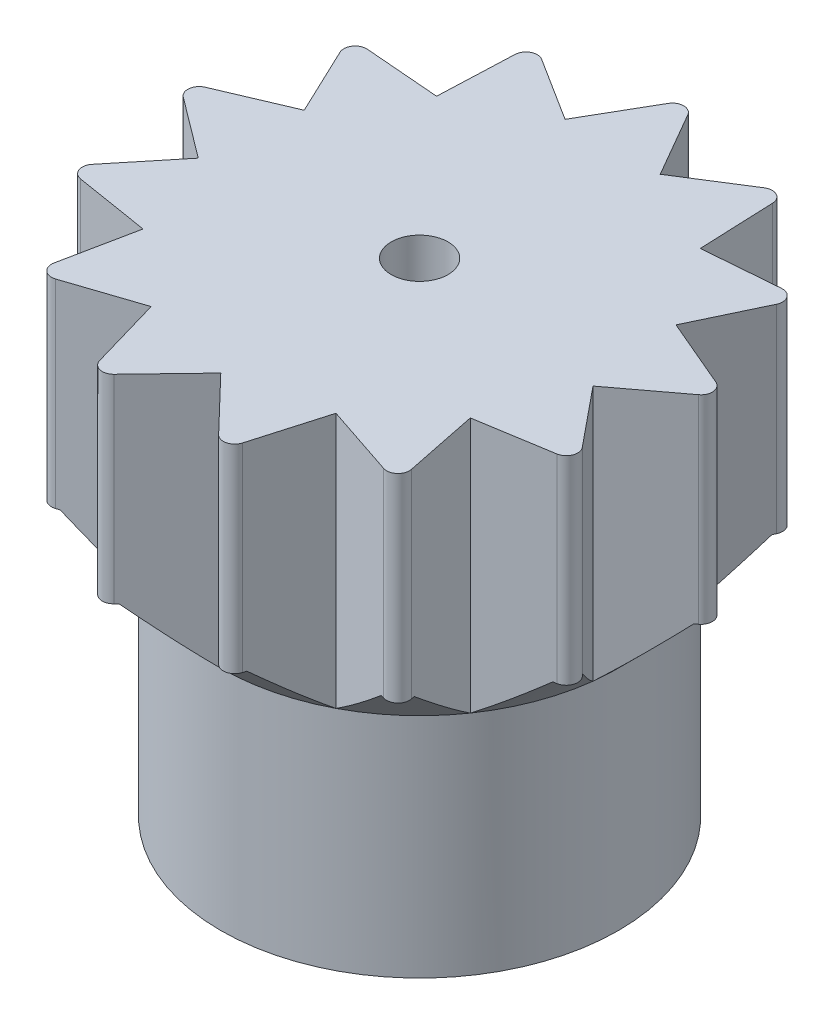
SolidWorks part; units mm, degrees
ref_plane "Front" through (0, 0, 0) normal (0, 0, 1) x (1, 0, 0)
ref_plane "Top" through (0, 0, 0) normal (0, 1, 0) x (1, 0, 0)
ref_plane "Right" through (0, 0, 0) normal (1, 0, 0) x (0, 0, -1)
sketch "Sketch1" plane through (0, 0, 0) normal (0, 1, 0) x (1, 0, 0)
  line L0 (2.3209, 2.6198) -> (3.9907, 2.7546)
  line L1 (3.9907, 2.7546) -> (3.2726, 1.2411)
  line L2 (3.2726, 1.2411) -> (4.8137, 0.5845)
  line L3 (4.8137, 0.5845) -> (3.4745, -0.4219)
  line L4 (3.4745, -0.4219) -> (4.534, -1.7195)
  line L5 (4.534, -1.7195) -> (2.8804, -1.9882)
  line L6 (2.8804, -1.9882) -> (3.2155, -3.6296)
  line L7 (3.2155, -3.6296) -> (1.6265, -3.0991)
  line L8 (1.6265, -3.0991) -> (1.1605, -4.7082)
  line L9 (1.1605, -4.7082) -> (0, -3.5)
  line L10 (0, -3.5) -> (-1.1605, -4.7082)
  line L11 (-1.1605, -4.7082) -> (-1.6265, -3.0991)
  line L12 (-1.6265, -3.0991) -> (-3.2155, -3.6296)
  line L13 (-3.2155, -3.6296) -> (-2.8804, -1.9882)
  line L14 (-2.8804, -1.9882) -> (-4.534, -1.7195)
  line L15 (-4.534, -1.7195) -> (-3.4745, -0.4219)
  line L16 (-3.4745, -0.4219) -> (-4.8137, 0.5845)
  line L17 (-4.8137, 0.5845) -> (-3.2726, 1.2411)
  line L18 (-3.2726, 1.2411) -> (-3.9907, 2.7546)
  line L19 (-3.9907, 2.7546) -> (-2.3209, 2.6198)
  line L20 (-2.3209, 2.6198) -> (-2.2535, 4.2936)
  line L21 (-2.2535, 4.2936) -> (-0.8376, 3.3983)
  line L22 (-0.8376, 3.3983) -> (0, 4.8491)
  line L23 (0, 4.8491) -> (0.8376, 3.3983)
  line L24 (0.8376, 3.3983) -> (2.2535, 4.2936)
  line L25 (2.2535, 4.2936) -> (2.3209, 2.6198)
  line L26 (-0.8376, 3.3983) -> (0.8376, 3.3983) construction
  circle A0 centre (0, 0) radius 3.5 construction
  circle A1 centre (0, 0) radius 0.5
  point P44 (0, 0)
  dimension "D2" = 7
  dimension "D4" = 1
  dimension "D3" = 60
  dimension "D5" = 1.6752
  dimension "D6" = 1.4508
  dimension "D1" = 13
extrude "Boss-Extrude1" add sketch "Sketch1" along normal blind 3.5
sketch "Sketch3" plane through (0, 0, 0) normal (0, -1, 0) x (1, 0, 0)
  circle A0 centre (0, 0) radius 3.5
  circle A1 centre (0, 0) radius 0.5
extrude "Boss-Extrude2" add sketch "Sketch3" along normal blind 5
sketch "Sketch2" plane through (0, -5, 0) normal (0, -1, 0) x (1, 0, 0)
  line L168 (-2.3565, -0.3552) -> (-2.394, -0.7385)
  line L169 (-2.5053, 0) -> (-2.3565, -0.3552)
  line L170 (-2.3565, 0.3552) -> (-2.5053, 0)
  line L171 (-2.394, 0.7385) -> (-2.3565, 0.3552)
  line L172 (-2.1471, 1.034) -> (-2.394, 0.7385)
  line L173 (-2.07, 1.4113) -> (-2.1471, 1.034)
  line L174 (-1.747, 1.6209) -> (-2.07, 1.4113)
  line L175 (-1.562, 1.9587) -> (-1.747, 1.6209)
  line L176 (-1.1916, 2.0639) -> (-1.562, 1.9587)
  line L177 (-0.9153, 2.3321) -> (-1.1916, 2.0639)
  line L178 (-0.5303, 2.3234) -> (-0.9153, 2.3321)
  line L179 (-0.1872, 2.4983) -> (-0.5303, 2.3234)
  line L180 (0.1781, 2.3765) -> (-0.1872, 2.4983)
  line L181 (0.5575, 2.4425) -> (0.1781, 2.3765)
  line L182 (0.8707, 2.2184) -> (0.5575, 2.4425)
  line L183 (1.2527, 2.1697) -> (0.8707, 2.2184)
  line L184 (1.4859, 1.8632) -> (1.2527, 2.1697)
  line L185 (1.8365, 1.704) -> (1.4859, 1.8632)
  line L186 (1.969, 1.3425) -> (1.8365, 1.704)
  line L187 (2.2572, 1.087) -> (1.969, 1.3425)
  line L188 (2.2773, 0.7024) -> (2.2572, 1.087)
  line L189 (2.4773, 0.3734) -> (2.2773, 0.7024)
  line L190 (2.3831, 0) -> (2.4773, 0.3734)
  line L191 (2.4773, -0.3734) -> (2.3831, 0)
  line L192 (2.2773, -0.7024) -> (2.4773, -0.3734)
  line L193 (2.2572, -1.087) -> (2.2773, -0.7024)
  line L194 (1.969, -1.3425) -> (2.2572, -1.087)
  line L195 (1.8365, -1.704) -> (1.969, -1.3425)
  line L196 (1.4859, -1.8632) -> (1.8365, -1.704)
  line L197 (1.2527, -2.1697) -> (1.4859, -1.8632)
  line L198 (0.8707, -2.2184) -> (1.2527, -2.1697)
  line L199 (0.5575, -2.4425) -> (0.8707, -2.2184)
  line L200 (0.1781, -2.3765) -> (0.5575, -2.4425)
  line L201 (-0.1872, -2.4983) -> (0.1781, -2.3765)
  line L202 (-0.5303, -2.3234) -> (-0.1872, -2.4983)
  line L203 (-0.9153, -2.3321) -> (-0.5303, -2.3234)
  line L204 (-1.1916, -2.0639) -> (-0.9153, -2.3321)
  line L205 (-1.562, -1.9587) -> (-1.1916, -2.0639)
  line L206 (-1.747, -1.6209) -> (-1.562, -1.9587)
  line L207 (-2.07, -1.4113) -> (-1.747, -1.6209)
  line L208 (-2.1471, -1.034) -> (-2.07, -1.4113)
  line L209 (-2.394, -0.7385) -> (-2.1471, -1.034)
  line L210 (-2.3565, -0.3552) -> (-2.394, -0.7385)
  line L211 (-2.5053, 0) -> (-2.3565, -0.3552)
  line L212 (-2.3565, 0.3552) -> (-2.5053, 0)
  line L213 (-2.394, 0.7385) -> (-2.3565, 0.3552)
  line L214 (-2.1471, 1.034) -> (-2.394, 0.7385)
  line L215 (-2.07, 1.4113) -> (-2.1471, 1.034)
  line L216 (-1.747, 1.6209) -> (-2.07, 1.4113)
  line L217 (-1.562, 1.9587) -> (-1.747, 1.6209)
  line L218 (-1.1916, 2.0639) -> (-1.562, 1.9587)
  line L219 (-0.9153, 2.3321) -> (-1.1916, 2.0639)
  line L220 (-0.5303, 2.3234) -> (-0.9153, 2.3321)
  line L221 (-0.1872, 2.4983) -> (-0.5303, 2.3234)
  line L222 (0.1781, 2.3765) -> (-0.1872, 2.4983)
  line L223 (0.5575, 2.4425) -> (0.1781, 2.3765)
  line L224 (0.8707, 2.2184) -> (0.5575, 2.4425)
  line L225 (1.2527, 2.1697) -> (0.8707, 2.2184)
  line L226 (1.4859, 1.8632) -> (1.2527, 2.1697)
  line L227 (1.8365, 1.704) -> (1.4859, 1.8632)
  line L228 (1.969, 1.3425) -> (1.8365, 1.704)
  line L229 (2.2572, 1.087) -> (1.969, 1.3425)
  line L230 (2.2773, 0.7024) -> (2.2572, 1.087)
  line L231 (2.4773, 0.3734) -> (2.2773, 0.7024)
  line L232 (2.3831, 0) -> (2.4773, 0.3734)
  line L233 (2.4773, -0.3734) -> (2.3831, 0)
  line L234 (2.2773, -0.7024) -> (2.4773, -0.3734)
  line L235 (2.2572, -1.087) -> (2.2773, -0.7024)
  line L236 (1.969, -1.3425) -> (2.2572, -1.087)
  line L237 (1.8365, -1.704) -> (1.969, -1.3425)
  line L238 (1.4859, -1.8632) -> (1.8365, -1.704)
  line L239 (1.2527, -2.1697) -> (1.4859, -1.8632)
  line L240 (0.8707, -2.2184) -> (1.2527, -2.1697)
  line L241 (0.5575, -2.4425) -> (0.8707, -2.2184)
  line L242 (0.1781, -2.3765) -> (0.5575, -2.4425)
  line L243 (-0.1872, -2.4983) -> (0.1781, -2.3765)
  line L244 (-0.5303, -2.3234) -> (-0.1872, -2.4983)
  line L245 (-0.9153, -2.3321) -> (-0.5303, -2.3234)
  line L246 (-1.1916, -2.0639) -> (-0.9153, -2.3321)
  line L247 (-1.562, -1.9587) -> (-1.1916, -2.0639)
  line L248 (-1.747, -1.6209) -> (-1.562, -1.9587)
  line L249 (-2.07, -1.4113) -> (-1.747, -1.6209)
  line L250 (-2.1471, -1.034) -> (-2.07, -1.4113)
  line L251 (-2.394, -0.7385) -> (-2.1471, -1.034)
  dimension "D1" = 0.1
extrude "Cut-Extrude1" cut sketch "Sketch2" against normal blind 3
fillet "Fillet1" radius 0.2 13 edges at (-4.8137, 1.75, -0.5845) (-4.534, 1.75, 1.7195) (-3.2155, 1.75, 3.6296) (-1.1605, 1.75, 4.7082) (1.1605, 1.75, 4.7082) (3.2155, 1.75, 3.6296) (4.534, 1.75, 1.7195) (4.8137, 1.75, -0.5845) (3.9907, 1.75, -2.7546) (2.2535, 1.75, -4.2936) (0, 1.75, -4.8491) (-2.2535, 1.75, -4.2936) (-3.9907, 1.75, -2.7546)
chamfer "Chamfer1" distance 1 angle 45 13 edges at (1.6265, 0, -3.0991) (2.8804, 0, -1.9882) (3.4745, 0, -0.4219) (3.2726, 0, 1.2411) (2.3209, 0, 2.6198) (0.8376, 0, 3.3983) (-0.8376, 0, 3.3983) (-2.3209, 0, 2.6198) (-3.2726, 0, 1.2411) (-3.4745, 0, -0.4219) (-2.8804, 0, -1.9882) (-1.6265, 0, -3.0991) (0, 0, -3.5)
